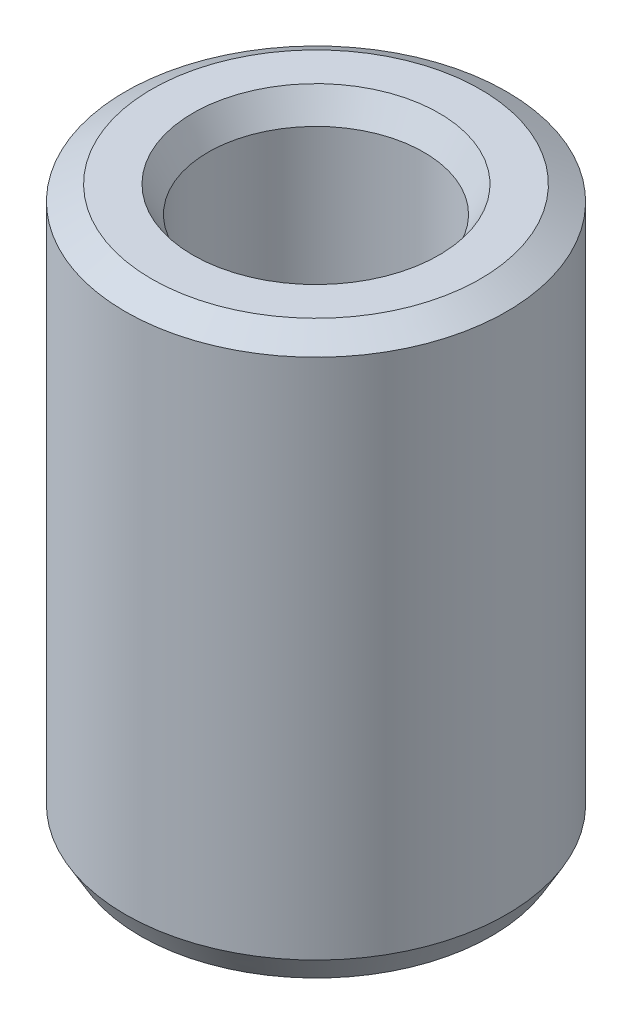
SolidWorks part; units mm, degrees
ref_plane "Front Plane" through (0, 0, 0) normal (0, 0, 1) x (1, 0, 0)
ref_plane "Top Plane" through (0, 0, 0) normal (0, 1, 0) x (1, 0, 0)
ref_plane "Right Plane" through (0, 0, 0) normal (1, 0, 0) x (0, 0, -1)
sketch "Sketch1" plane through (0, 0, 0) normal (0, 1, 0) x (1, 0, 0)
  circle A0 centre (0, 0) radius 7.5
  dimension "SLEEVE_OD" = 15
extrude "Boss-Extrude1" add sketch "Sketch1" along normal blind 22.1695
sketch "Sketch2" plane through (0, 0, 0) normal (0, 1, 0) x (1, 0, 0)
  circle A0 centre (0, 0) radius 4.2444
  dimension "BORE_D" = 8.4887
extrude "Cut-Extrude1" cut sketch "Sketch2" along normal through all
chamfer "Chamfer1" distance 0.5972 angle 60 4 edges at (0, 22.1695, 4.2444) (0, 0, 4.2444) (0, 0, 7.5) (0, 22.1695, 7.5) first distance on face at (0, 22.1695, 4.2444) first distance on face at (0, 0, 4.2444) first distance on face at (0, 22.1695, 7.5)
